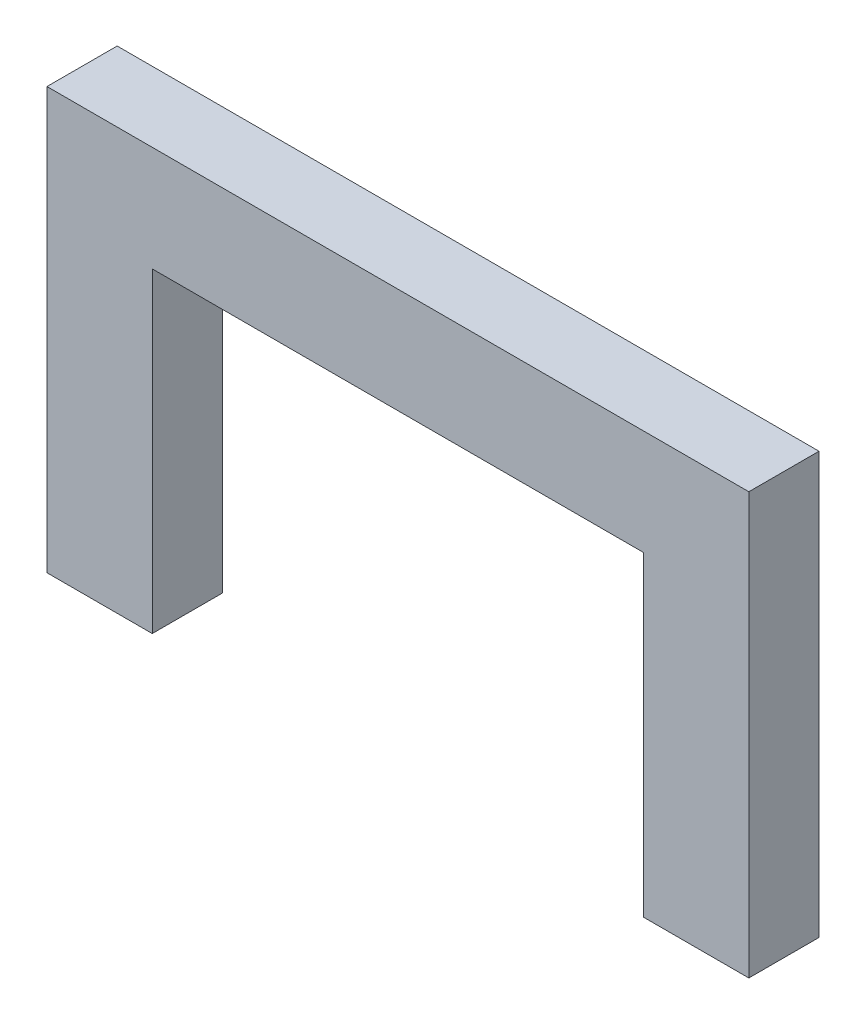
SolidWorks part; units mm, degrees
ref_plane "Front" through (0, 0, 0) normal (0, 0, 1) x (1, 0, 0)
ref_plane "Top" through (0, 0, 0) normal (0, 1, 0) x (1, 0, 0)
ref_plane "Right" through (0, 0, 0) normal (1, 0, 0) x (0, 0, -1)
sketch "Sketch2" plane through (0, 0, 0) normal (0, 0, 1) x (1, 0, 0)
  line L1 (-46.8509, 36.2152) -> (80.1491, 36.2152)
  line L2 (-46.8509, 36.2152) -> (-46.8509, -39.9848)
  line L3 (-46.8509, -39.9848) -> (80.1491, -39.9848)
  line L4 (80.1491, 36.2152) -> (80.1491, -39.9848)
  line L5 (-27.8009, -39.9848) -> (61.0991, -39.9848)
  line L6 (-27.8009, -39.9848) -> (-27.8009, 17.1652)
  line L7 (-27.8009, 17.1652) -> (61.0991, 17.1652)
  line L8 (61.0991, -39.9848) -> (61.0991, 17.1652)
  dimension "D1" = 76.2
  dimension "D2" = 127
  dimension "D3" = 19.05
  dimension "D4" = 19.05
  dimension "D5" = 19.05
extrude "Boss-Extrude1" add sketch "Sketch2" along normal blind 12.7 contours L8 L3 L4 L1 L2 L6 L7 region at (16.6491, 34.7341, 0)
